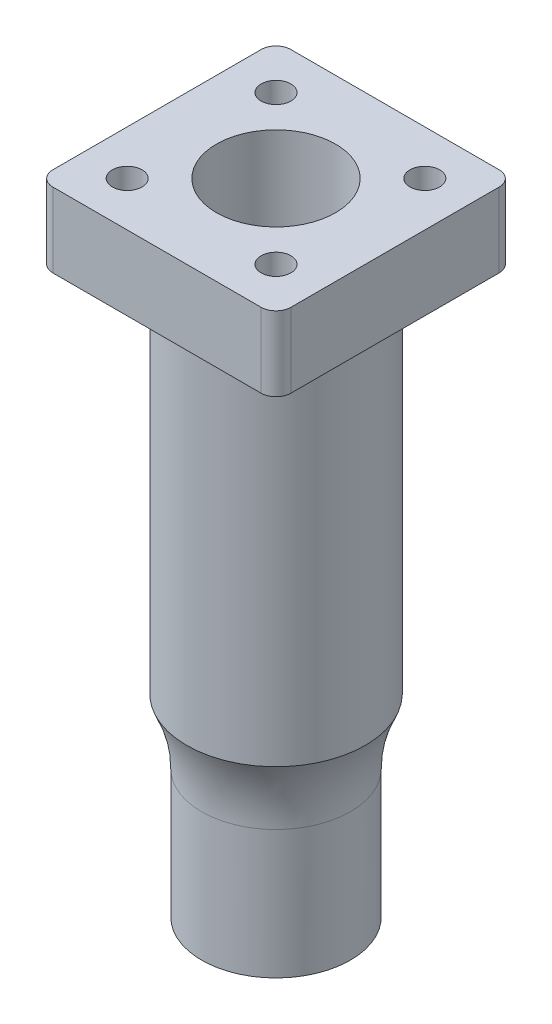
SolidWorks part; units mm, degrees
ref_plane "Front Plane" through (0, 0, 0) normal (0, 0, 1) x (1, 0, 0)
ref_plane "Top Plane" through (0, 0, 0) normal (0, 1, 0) x (1, 0, 0)
ref_plane "Right Plane" through (0, 0, 0) normal (1, 0, 0) x (0, 0, -1)
sketch "Sketch1" plane through (0, 0, 0) normal (0, 1, 0) x (1, 0, 0)
  circle A0 centre (0, 0) radius 2.25
  circle A1 centre (0, 0) radius 5
extrude "Boss-Extrude1" add sketch "Sketch1" along normal blind 3
sketch "Sketch2" plane through (0, 0, 0) normal (0, -1, 0) x (1, 0, 0)
  circle A0 centre (0, 0) radius 5
  circle A1 centre (0, 0) radius 3
extrude "Boss-Extrude2" add sketch "Sketch2" along normal blind 10
sketch "Sketch3" plane through (0, 3, 0) normal (0, 1, 0) x (1, 0, 0)
  circle A0 centre (0, 0) radius 6
  circle A1 centre (0, 0) radius 4
extrude "Boss-Extrude3" add sketch "Sketch3" along normal blind 30
fillet "Fillet1" radius 10 1 edges at (0, 3, 5)
sketch "Sketch4" plane through (0, 33, 0) normal (0, 1, 0) x (1, 0, 0)
  line L1 (-10, 10) -> (10, -10) construction
  line L6 (-6.6, 0) -> (6.6, 0) construction
  line L17 (10, 10) -> (-10, -10) construction
  line L18 (-10, 0) -> (0, 10) construction
  line L19 (0, 10) -> (10, 0) construction
  line L20 (10, 0) -> (0, -10) construction
  line L21 (-10, 0) -> (0, -10) construction
  line L22 (-8, 0) -> (-8, 7)
  line L23 (-7, 8) -> (7, 8)
  line L24 (8, 7) -> (8, -7)
  line L25 (7, -8) -> (-7, -8)
  line L26 (-8, -7) -> (-8, 0)
  circle A1 centre (0, 0) radius 4
  circle A2 centre (-5, 5) radius 1
  circle A3 centre (5, 5) radius 1
  circle A4 centre (-5, -5) radius 1
  circle A5 centre (5, -5) radius 1
  arc A6 (-7, 8) -> (-8, 7) centre (-7, 7) ccw
  arc A7 (8, 7) -> (7, 8) centre (7, 7) ccw
  arc A8 (7, -8) -> (8, -7) centre (7, -7) ccw
  arc A9 (-7, -8) -> (-8, -7) centre (-7, -7) cw
  dimension "D1" = 1
  dimension "D2" = 1
  dimension "D3" = 1
  dimension "1" = 1
extrude "Boss-Extrude4" add sketch "Sketch4" against normal blind 5
